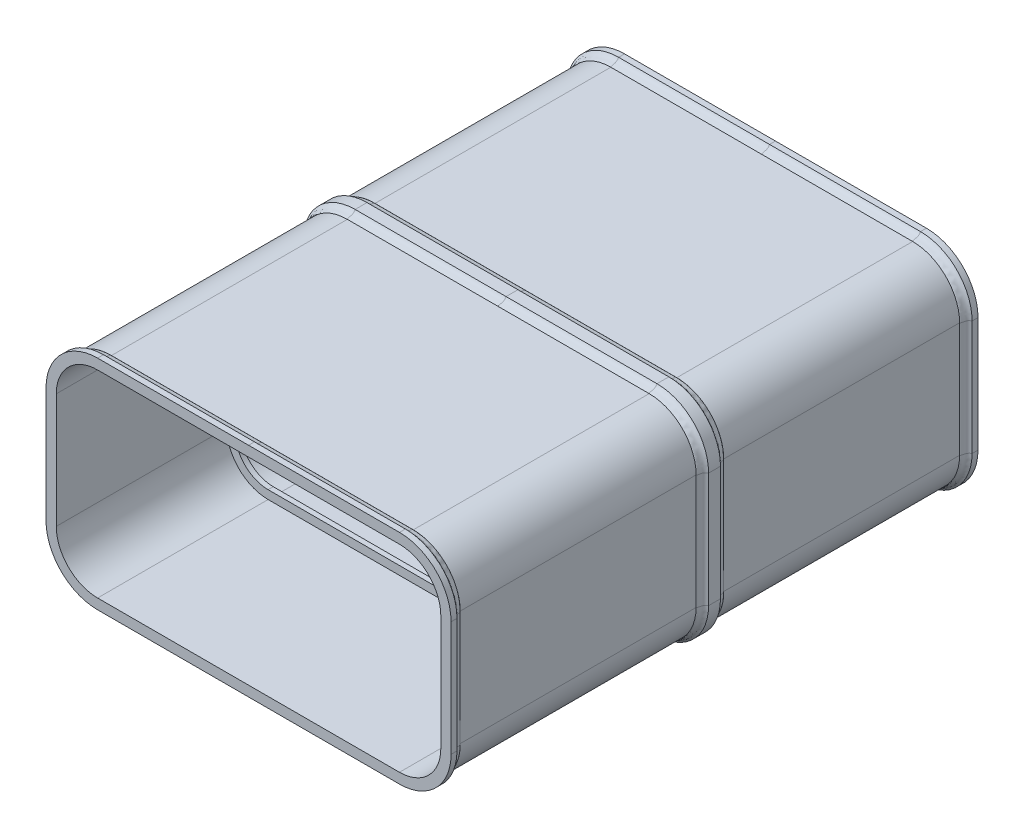
SolidWorks part; units mm, degrees
ref_plane "Front Plane" through (0, 0, 0) normal (0, 0, 1) x (1, 0, 0)
ref_plane "Top Plane" through (0, 0, 0) normal (0, 1, 0) x (1, 0, 0)
ref_plane "Right Plane" through (0, 0, 0) normal (1, 0, 0) x (0, 0, -1)
sketch "Sketch1" plane through (0, 0, 0) normal (0, 0, 1) x (1, 0, 0)
  line L0 (115.6416, -33.5473) -> (115.6416, 33.5473)
  line L6 (-88.2163, 60.9727) -> (88.2163, 60.9727)
  line L7 (-115.6416, -33.5473) -> (-115.6416, 33.5473)
  line L8 (-88.2163, -60.9727) -> (88.2163, -60.9727)
  arc A4 (88.2163, 60.9727) -> (115.6416, 33.5473) centre (88.2163, 33.5473) cw
  arc A5 (-88.2163, 60.9727) -> (-115.6416, 33.5473) centre (-88.2163, 33.5473) ccw
  arc A6 (-88.2163, -60.9727) -> (-115.6416, -33.5473) centre (-88.2163, -33.5473) cw
  arc A7 (88.2163, -60.9727) -> (115.6416, -33.5473) centre (88.2163, -33.5473) ccw
extrude "Boss-Extrude1" add sketch "Sketch1" along normal mid plane 308
ref_plane "Plane1" through (0, 0, 0) normal (1, 0, 0) x (0, 0, -1)
sketch "Sketch2" plane through (0, 0, 0) normal (1, 0, 0) x (0, 0, -1)
  line L0 (154, 3.0542) -> (154, 57.7166) construction
  line L1 (154, -33.5473) -> (154, 33.5473) construction
  line L16 (150.5297, 63.7129) -> (157.4703, 63.7129)
  line L17 (145.9383, 60.873) -> (162.0617, 60.873)
  line L18 (154, 60.873) -> (154, 66.5528) construction
  spline S4 degree 3 poles (150.5297, 63.7129) (150.5048, 63.6791) (150.4645, 63.6187) (150.3398, 63.4169) (150.1499, 63.0879) (149.7688, 62.6228) (149.199, 62.1768) (148.4365, 61.8464) (147.576, 61.6607) (146.8409, 61.5309) (146.4044, 61.3925) (146.1977, 61.2734) (146.0964, 61.1827) (146.0188, 61.0842) (145.9579, 60.939) (145.9383, 60.873) knots 0.125808 0.125808 0.125808 0.125808 0.153126 0.180445 0.235082 0.289719 0.344356 0.45363 0.562904 0.672178 0.781452 0.836089 0.890726 0.945363 1 1 1 1
  spline S5 degree 3 poles (162.0617, 60.873) (162.0421, 60.939) (161.9812, 61.0842) (161.9036, 61.1827) (161.8023, 61.2734) (161.5956, 61.3925) (161.1591, 61.5309) (160.424, 61.6607) (159.5635, 61.8464) (158.801, 62.1768) (158.2312, 62.6228) (157.8501, 63.0879) (157.6602, 63.4169) (157.5355, 63.6187) (157.4952, 63.6791) (157.4703, 63.7129) knots 0.125808 0.125808 0.125808 0.125808 0.180445 0.235082 0.289719 0.344356 0.45363 0.562904 0.672178 0.781452 0.836089 0.890726 0.945363 0.972681 1 1 1 1
  point P2 (154, 63.7129)
  point P4 (154, 3.0542)
sketch "Sketch3" plane through (0, 0, -154) normal (0, 0, -1) x (-1, 0, 0)
  line L4 (115.6416, 33.5473) -> (115.6416, -33.5473)
  line L5 (88.2163, -60.9727) -> (-88.2163, -60.9727)
  line L6 (-115.6416, -33.5473) -> (-115.6416, 33.5473)
  line L7 (-88.2163, 60.9727) -> (88.2163, 60.9727)
  arc A4 (115.6416, 33.5473) -> (88.2163, 60.9727) centre (88.2163, 33.5473) ccw
  arc A5 (88.2163, -60.9727) -> (115.6416, -33.5473) centre (88.2163, -33.5473) ccw
  arc A6 (-115.6416, -33.5473) -> (-88.2163, -60.9727) centre (-88.2163, -33.5473) ccw
  arc A7 (-88.2163, 60.9727) -> (-115.6416, 33.5473) centre (-88.2163, 33.5473) ccw
sweep "Sweep3" add profiles "Sketch2" path "Sketch3"
pattern_linear "LPattern1" count 3 spacing 154.0089 along (0, 0, 1) of "Sweep3"
sketch "Sketch4" plane through (-115.6416, 0, 0) normal (-1, 0, 0) x (0, 0, 1)
  line L0 (-153.99, 60.9727) -> (-153.99, -60.9727)
  line L1 (154, -60.9727) -> (-154, -60.9727) construction
  line L2 (-153.99, -60.9727) -> (-153.99, -86.9232)
  line L3 (-153.99, -86.9232) -> (-259.8552, -86.9232)
  line L4 (-259.8552, -86.9232) -> (-259.8552, 97.9165)
  line L5 (-259.8552, 97.9165) -> (-153.99, 97.9165)
  line L6 (-153.99, 97.9165) -> (-153.99, 60.9727)
  line L7 (153.99, 97.9165) -> (153.99, -98.874)
  line L8 (153.99, -98.874) -> (281.8266, -98.874)
  line L9 (281.8266, -98.874) -> (281.8266, 97.9165)
  line L10 (281.8266, 97.9165) -> (153.99, 97.9165)
  line L11 (-154, 33.5473) -> (-154, -33.5473) construction
  line L12 (154, 33.5473) -> (154, -33.5473) construction
  dimension "D1" = 0.01
  dimension "D2" = 0.01
extrude "Cut-Extrude2" cut sketch "Sketch4" against normal through all both and the other way through all
sketch "Sketch6" plane through (0, 0, 153.99) normal (0, 0, 1) x (1, 0, 0)
  line L8 (-88.2163, -57.7129) -> (88.2163, -57.7129)
  line L9 (-88.2163, -57.7129) -> (88.2163, -57.7129)
  line L10 (112.3819, -33.5473) -> (112.3819, 33.5473)
  line L11 (112.3819, -33.5473) -> (112.3819, 33.5473)
  line L17 (88.2163, 57.7129) -> (0, 57.7129)
  line L18 (88.2163, 57.7129) -> (0, 57.7129)
  line L19 (0, 57.7129) -> (-88.2163, 57.7129)
  line L20 (0, 57.7129) -> (-88.2163, 57.7129)
  line L21 (-112.3819, 33.5473) -> (-112.3819, -33.5473)
  line L22 (-112.3819, 33.5473) -> (-112.3819, -33.5473)
  arc A8 (88.2163, -57.7129) -> (112.3819, -33.5473) centre (88.2163, -33.5473) ccw
  arc A9 (88.2163, -57.7129) -> (112.3819, -33.5473) centre (88.2163, -33.5473) ccw
  arc A10 (112.3819, 33.5473) -> (88.2163, 57.7129) centre (88.2163, 33.5473) ccw
  arc A11 (112.3819, 33.5473) -> (88.2163, 57.7129) centre (88.2163, 33.5473) ccw
  arc A16 (-88.2163, 57.7129) -> (-112.3819, 33.5473) centre (-88.2163, 33.5473) ccw
  arc A17 (-88.2163, 57.7129) -> (-112.3819, 33.5473) centre (-88.2163, 33.5473) ccw
  arc A18 (-112.3819, -33.5473) -> (-88.2163, -57.7129) centre (-88.2163, -33.5473) ccw
  arc A19 (-112.3819, -33.5473) -> (-88.2163, -57.7129) centre (-88.2163, -33.5473) ccw
  dimension "D1" = 6
extrude "Cut-Extrude3" cut sketch "Sketch6" against normal through all both
ref_plane "Plane2" through (88.2163, 57.7129, -153.99) normal (-1, 0, 0) x (0, 0, 1)
sketch "Sketch9" plane through (0, 0, -153.99) normal (0, 0, -1) x (-1, 0, 0)
  line L0 (112.3819, 33.5473) -> (112.3819, -33.5473) construction
  line L1 (88.2163, -57.7129) -> (-88.2163, -57.7129) construction
  line L2 (-112.3819, -33.5473) -> (-112.3819, 33.5473) construction
  line L3 (-88.2163, 57.7129) -> (88.2163, 57.7129) construction
  line L4 (112.3819, 33.5473) -> (112.3819, -33.5473)
  line L5 (88.2163, -57.7129) -> (-88.2163, -57.7129)
  line L6 (-112.3819, -33.5473) -> (-112.3819, 33.5473)
  line L7 (-88.2163, 57.7129) -> (88.2163, 57.7129)
  line L8 (-107.3819, -33.5473) -> (-107.3819, 33.5473)
  line L9 (-88.2163, 52.7129) -> (88.2163, 52.7129)
  line L10 (107.3819, 33.5473) -> (107.3819, -33.5473)
  line L11 (88.2163, -52.7129) -> (-88.2163, -52.7129)
  arc A0 (112.3819, 33.5473) -> (88.2163, 57.7129) centre (88.2163, 33.5473) ccw construction
  arc A1 (88.2163, -57.7129) -> (112.3819, -33.5473) centre (88.2163, -33.5473) ccw construction
  arc A2 (-112.3819, -33.5473) -> (-88.2163, -57.7129) centre (-88.2163, -33.5473) ccw construction
  arc A3 (-88.2163, 57.7129) -> (-112.3819, 33.5473) centre (-88.2163, 33.5473) ccw construction
  arc A4 (112.3819, 33.5473) -> (88.2163, 57.7129) centre (88.2163, 33.5473) ccw
  arc A5 (88.2163, -57.7129) -> (112.3819, -33.5473) centre (88.2163, -33.5473) ccw
  arc A6 (-112.3819, -33.5473) -> (-88.2163, -57.7129) centre (-88.2163, -33.5473) ccw
  arc A7 (-88.2163, 57.7129) -> (-112.3819, 33.5473) centre (-88.2163, 33.5473) ccw
  arc A8 (-88.2163, 52.7129) -> (-107.3819, 33.5473) centre (-88.2163, 33.5473) ccw
  arc A9 (107.3819, 33.5473) -> (88.2163, 52.7129) centre (88.2163, 33.5473) ccw
  arc A10 (88.2163, -52.7129) -> (107.3819, -33.5473) centre (88.2163, -33.5473) ccw
  arc A11 (-107.3819, -33.5473) -> (-88.2163, -52.7129) centre (-88.2163, -33.5473) ccw
  dimension "D1" = 5
extrude "Boss-Extrude2" add sketch "Sketch9" against normal blind 3
fillet "Fillet1" radius 1 16 edges at (-101.7684, 47.0995, -150.99) (-107.3819, 0, -150.99) (-101.7684, -47.0995, -150.99) (0, -52.7129, -150.99) (101.7684, -47.0995, -150.99) (107.3819, 0, -150.99) (101.7684, 47.0995, -150.99) (-101.7684, 47.0995, -153.99) (-107.3819, 0, -153.99) (-101.7684, -47.0995, -153.99) (0, -52.7129, -153.99) (101.7684, -47.0995, -153.99) (107.3819, 0, -153.99) (101.7684, 47.0995, -153.99) (0, 52.7129, -150.99) (0, 52.7129, -153.99)
pattern_linear "LPattern2" count 3 spacing 102.66 along (0, 0, 1) of "Boss-Extrude2"
